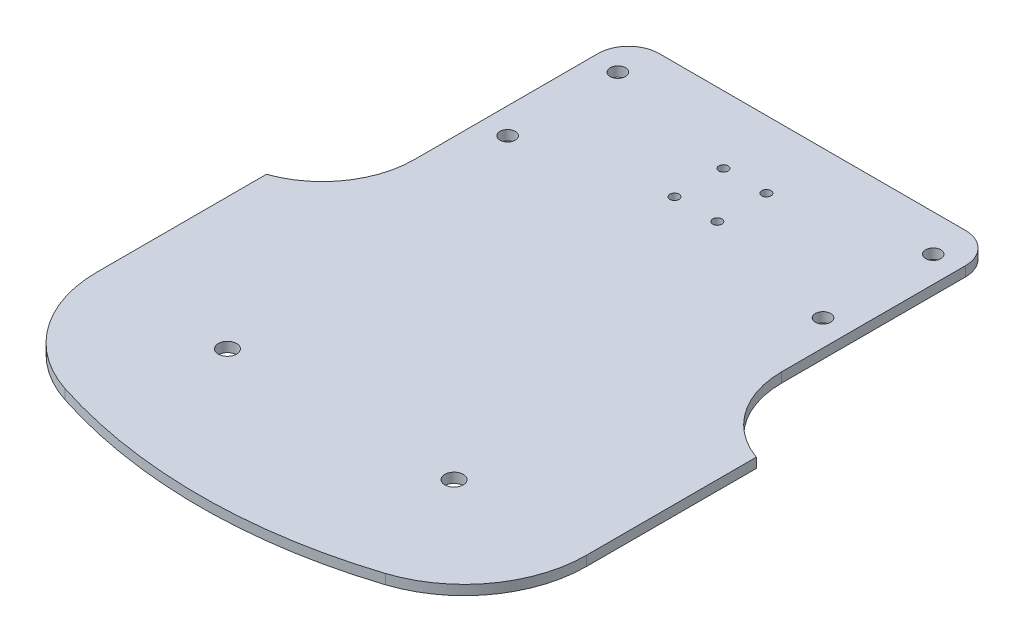
SolidWorks part; units mm, degrees
other "main"
material "Skleněné vlákno-A"
ref_plane "Přední rovina" through (0, 0, 0) normal (0, 0, 1) x (1, 0, 0)
ref_plane "Horní rovina" through (0, 0, 0) normal (0, 1, 0) x (1, 0, 0)
ref_plane "Pravá rovina" through (0, 0, 0) normal (1, 0, 0) x (0, 0, -1)
sketch "Skica1" plane through (0, 0, 0) normal (0, 1, 0) x (1, 0, 0)
  line L0 (0, 0) -> (-30, 0) construction
  line L1 (-25, 15) -> (25, 15)
  line L2 (-30, 10) -> (-30, -20)
  line L3 (0, -85) -> (-40, -85) construction
  line L4 (30, 10) -> (30, -20)
  line L5 (-40, -61.8466) -> (-40, -34.1421)
  line L6 (0, -154.3556) -> (0, 117.2396) construction
  line L7 (40, -61.8466) -> (40, -34.1421)
  arc A0 (-30, -20) -> (-40, -34.1421) centre (-45, -20) cw
  arc A1 (-25, 15) -> (-30, 10) centre (-25, 10) ccw
  arc A2 (26.1538, -80.8763) -> (-26.1538, -80.8763) centre (0, 0) cw
  arc A3 (25, 15) -> (30, 10) centre (25, 10) cw
  arc A4 (30, -20) -> (40, -34.1421) centre (45, -20) ccw
  arc A5 (40, -61.8466) -> (26.1538, -80.8763) centre (20, -61.8466) cw
  arc A6 (-26.1538, -80.8763) -> (-40, -61.8466) centre (-20, -61.8466) cw
  point P8 (32.3438, 20)
  point P13 (-30, 15)
  point P24 (0, 15)
  point P26 (40, -75)
  point P29 (-40, -75)
  dimension "D4" = 5
  dimension "D2" = 100
  dimension "D5" = 80
  dimension "D7" = 15
  dimension "D8" = 20
  dimension "D1" = 60
  dimension "D3" = 15
  dimension "D6" = 20
extrude "Přidat vysunutím1" add sketch "Skica1" along normal mid plane 1.6
sketch "Skica2" plane through (0, -0.8, 0) normal (0, -1, 0) x (1, 0, 0)
  circle A0 centre (-25.75, -9) radius 1.25 construction
  circle A1 centre (-25.75, -9) radius 1.25
  circle A2 centre (-25.75, 9) radius 1.25 construction
  circle A3 centre (25.75, 9) radius 1.25 construction
  circle A4 centre (25.75, -9) radius 1.25 construction
  circle A5 centre (-25.75, 9) radius 1.25
  circle A6 centre (25.75, 9) radius 1.25
  circle A7 centre (25.75, -9) radius 1.25
extrude "Odebrat vysunutím1" cut sketch "Skica2" against normal through all
sketch "Skica3" plane through (0, -0.8, 0) normal (0, -1, 0) x (1, 0, 0)
  line L0 (0, 0) -> (14.3407, 0) construction
  line L1 (0, 0) -> (0, 8.7788) construction
  circle A0 centre (-3.5, 4) radius 0.75
  circle A1 centre (3.5, 4) radius 0.75
  circle A2 centre (-3.5, -4) radius 0.75
  circle A3 centre (3.5, -4) radius 0.75
  dimension "D1" = 8
  dimension "D2" = 7
  dimension "D3" = 1.5
extrude "Odebrat vysunutím2" cut sketch "Skica3" against normal through all
sketch "Skica8" plane through (0, -0.8, 0) normal (0, -1, 0) x (1, 0, 0)
  circle A0 centre (18.5, 62) radius 1.5 construction
  circle A1 centre (18.5, 62) radius 1.5
  circle A2 centre (-18.5, 62) radius 1.5 construction
  circle A3 centre (-18.5, 62) radius 1.5
extrude "Odebrat vysunutím4" cut sketch "Skica8" against normal through all
sketch "Skica5" plane through (0, -0.8, 0) normal (0, -1, 0) x (1, 0, 0)
  line L0 (40, 61.8466) -> (40, 34.1421) construction
  line L2 (-40, 34.1421) -> (-40, 61.8466) construction
  arc A0 (26.1538, 80.8763) -> (-26.1538, 80.8763) centre (0, 0) ccw construction
  circle A1 centre (-22.7593, 74.6057) radius 0.25
  circle A2 centre (-30, 72) radius 0.25
  circle A3 centre (-15.2971, 76.4853) radius 0.25
  circle A4 centre (-7.6859, 77.6204) radius 0.25
  circle A5 centre (0, 78) radius 0.25
  circle A6 centre (7.6859, 77.6204) radius 0.25
  circle A7 centre (15.2971, 76.4853) radius 0.25
  circle A8 centre (22.7593, 74.6057) radius 0.25
  circle A9 centre (30, 72) radius 0.25
  arc A10 (26.1538, 80.8763) -> (-26.1538, 80.8763) centre (0, 0) ccw construction
  point P28 (0, 85)
  dimension "D1" = 7
  dimension "D4" = 0.5
  dimension "D5" = 10
  dimension "D6" = 7
  dimension "D7" = 7
  dimension "D8" = 7.6953
  dimension "D2" = 10
  dimension "D3" = 9
sketch "keepouts" plane through (0, -0.8, 0) normal (0, -1, 0) x (1, 0, 0)
  line L0 (-21.5, 7) -> (-21.5, 8.25) construction
  line L1 (-29.5, 7) -> (-19, 7) construction
  line L2 (-21.5, -8.25) -> (-21.5, -7) construction
  line L3 (-21.5, -7) -> (-19, -7) construction
  line L4 (-21.5, 7) -> (-21.5, 8.25)
  line L5 (-21.5, 7) -> (-19, 7)
  line L6 (-21.5, -8.25) -> (-21.5, -7)
  line L7 (-21.5, -7) -> (-19, -7)
  line L8 (18.5, 11) -> (18.5, 29)
  line L9 (-16.5, 9) -> (16.5, 9)
  line L10 (-18.5, 29) -> (-18.5, 11)
  line L11 (16.5, 31) -> (-16.5, 31)
  line L12 (18.5, 11) -> (18.5, 29)
  line L13 (-16.5, 9) -> (16.5, 9)
  line L14 (-18.5, 29) -> (-18.5, 11)
  line L15 (16.5, 31) -> (-16.5, 31)
  line L16 (-4.8, -2.5) -> (-4.8, 2.5) construction
  line L17 (-19, 7) -> (-4.8, 7)
  line L18 (21.5, 8.25) -> (21.5, 7) construction
  line L19 (-19, -7) -> (-4.8, -7)
  line L20 (-4.8, 7) -> (-4.8, -7)
  line L21 (21.5, 8.25) -> (21.5, 7)
  line L22 (19, 7) -> (29.5, 7) construction
  line L23 (19, 7) -> (21.5, 7)
  line L24 (29.5, -7) -> (19, -7) construction
  line L25 (21.5, -7) -> (21.5, -8.25) construction
  line L26 (21.5, -7) -> (19, -7)
  line L27 (21.5, -7) -> (21.5, -8.25)
  line L28 (4.8, 2.5) -> (4.8, -2.5) construction
  line L29 (19, 7) -> (4.8, 7)
  line L30 (-22.5, 57) -> (-22.5, 62) construction
  line L31 (19, -7) -> (4.8, -7)
  line L32 (4.8, 7) -> (4.8, -7)
  line L33 (-22.5, 55) -> (-14.5, 55) construction
  line L34 (-14.5, 55) -> (-14.5, 57) construction
  line L35 (-14.5, 57) -> (-14.5, 62) construction
  line L36 (-22.5, 57) -> (-22.5, 55) construction
  line L37 (-22.5, 57) -> (-22.5, 62)
  line L38 (-22.5, 55) -> (-14.5, 55)
  line L39 (-14.5, 55) -> (-14.5, 57)
  line L40 (-14.5, 57) -> (-14.5, 62)
  line L41 (-22.5, 57) -> (-22.5, 55)
  line L42 (22.5, 57) -> (22.5, 62) construction
  line L43 (22.5, 55) -> (22.5, 57) construction
  line L44 (14.5, 55) -> (22.5, 55) construction
  line L45 (14.5, 57) -> (14.5, 55) construction
  line L46 (14.5, 57) -> (14.5, 62) construction
  line L47 (22.5, 57) -> (22.5, 62)
  line L48 (22.5, 55) -> (22.5, 57)
  line L49 (14.5, 55) -> (22.5, 55)
  line L50 (14.5, 57) -> (14.5, 55)
  line L51 (14.5, 57) -> (14.5, 62)
  arc A0 (-21.5, 8.25) -> (-30, 8.25) centre (-25.75, 8.25) ccw construction
  arc A1 (-30, -8.25) -> (-21.5, -8.25) centre (-25.75, -8.25) ccw construction
  arc A2 (-21.5, 8.25) -> (-30, 8.25) centre (-25.75, 8.25) ccw
  arc A3 (-30, -8.25) -> (-21.5, -8.25) centre (-25.75, -8.25) ccw
  arc A4 (30, 8.25) -> (21.5, 8.25) centre (25.75, 8.25) ccw construction
  arc A5 (30, 8.25) -> (21.5, 8.25) centre (25.75, 8.25) ccw
  arc A6 (21.5, -8.25) -> (30, -8.25) centre (25.75, -8.25) ccw construction
  arc A7 (21.5, -8.25) -> (30, -8.25) centre (25.75, -8.25) ccw
  arc A8 (18.5, 29) -> (16.5, 31) centre (16.5, 29) ccw
  arc A9 (16.5, 9) -> (18.5, 11) centre (16.5, 11) ccw
  arc A10 (-18.5, 11) -> (-16.5, 9) centre (-16.5, 11) ccw
  arc A11 (-16.5, 31) -> (-18.5, 29) centre (-16.5, 29) ccw
  arc A12 (18.5, 29) -> (16.5, 31) centre (16.5, 29) ccw
  arc A13 (16.5, 9) -> (18.5, 11) centre (16.5, 11) ccw
  arc A14 (-18.5, 11) -> (-16.5, 9) centre (-16.5, 11) ccw
  arc A15 (-16.5, 31) -> (-18.5, 29) centre (-16.5, 29) ccw
  arc A16 (-14.5, 62) -> (-22.5, 62) centre (-18.5, 62) ccw construction
  arc A17 (-14.5, 62) -> (-22.5, 62) centre (-18.5, 62) ccw
  arc A18 (22.5, 62) -> (14.5, 62) centre (18.5, 62) ccw construction
  arc A19 (22.5, 62) -> (14.5, 62) centre (18.5, 62) ccw
  dimension "D1" = 1
